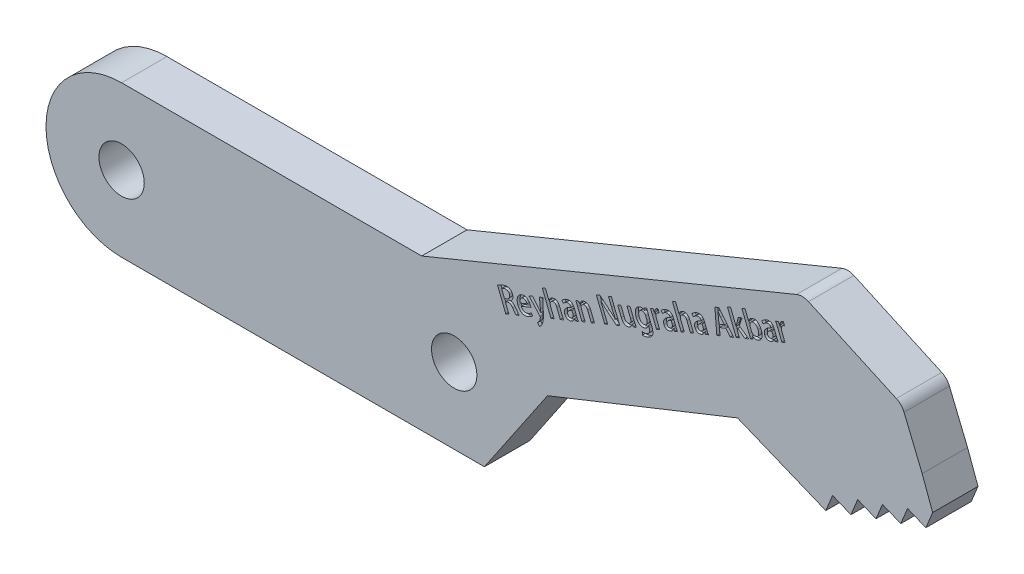
SolidWorks part; units mm, degrees
ref_plane "Front Plane" through (0, 0, 0) normal (0, 0, 1) x (1, 0, 0)
ref_plane "Top Plane" through (0, 0, 0) normal (0, 1, 0) x (1, 0, 0)
ref_plane "Right Plane" through (0, 0, 0) normal (1, 0, 0) x (0, 0, -1)
sketch "Sketch1" plane through (0, 0, 0) normal (0, 0, 1) x (1, 0, 0)
  line L0 (0, 0) -> (22, 0) construction
  line L1 (0, 5) -> (19.85, 5)
  line L2 (0, -5) -> (22, -5)
  line L3 (19.85, 5) -> (44.6431, 15.1937)
  line L4 (45.4379, 15.1788) -> (51.2451, 12.5335)
  line L5 (51.7554, 12.0038) -> (52.955, 9.0863)
  line L6 (24, -5) -> (22, -5)
  line L7 (24, -5) -> (28.1744, 1.1586)
  line L8 (28.1744, 1.1586) -> (40.742, 6.17)
  line L9 (40.742, 6.17) -> (46.5818, 3.7797)
  line L10 (46.5818, 3.7797) -> (47.0288, 4.8718)
  line L11 (47.0288, 4.8718) -> (48.2418, 4.3753)
  line L12 (48.2418, 4.3753) -> (48.6888, 5.4674)
  line L13 (48.6888, 5.4674) -> (49.9018, 4.9709)
  line L14 (49.9018, 4.9709) -> (50.3274, 6.0107)
  line L15 (50.3274, 6.0107) -> (51.5404, 5.5142)
  line L16 (51.5404, 5.5142) -> (51.9874, 6.6063)
  line L17 (51.9874, 6.6063) -> (53.2004, 6.1098)
  line L18 (53.2004, 6.1098) -> (53.6474, 7.2018)
  line L19 (53.6474, 7.2018) -> (52.955, 9.0863)
  arc A0 (0, 5) -> (0, -5) centre (0, 0) ccw
  circle A2 centre (0, 0) radius 1.5
  circle A3 centre (22, 0) radius 1.5
  arc A4 (51.2451, 12.5335) -> (51.7554, 12.0038) centre (50.8306, 11.6235) cw
  arc A5 (44.6431, 15.1937) -> (45.4379, 15.1788) centre (45.0233, 14.2688) cw
  point P3 (11, 0)
  point P18 (51.605, 12.3696)
  point P21 (45.0437, 15.3584)
  point P22 (24, -5)
  dimension "D3" = 3
  dimension "D4" = 3
  dimension "D12" = 1
  dimension "D2" = 5
  dimension "D5" = 19.85
  dimension "D6" = 157.65
  dimension "D7" = 27.24
  dimension "D8" = 133.16
  dimension "D9" = 7.21
  dimension "D10" = 136.84
  dimension "D11" = 3.55
  dimension "D13" = 24
  dimension "D14" = 55.87
  dimension "D15" = 7.44
  dimension "D16" = 214.13
  dimension "D17" = 13.53
  dimension "D18" = 224
  dimension "D19" = 6.31
  dimension "D20" = 1.18
  dimension "D21" = 1.66
  dimension "D22" = 2.0076
  dimension "D23" = 10
  dimension "D24" = 22
  dimension "D25" = 5
  dimension "D26" = 5
  dimension "D27" = 137.564
extrude "Boss-Extrude1" add sketch "Sketch1" along normal blind 3
sketch "Sketch2" plane through (0, 0, 3) normal (0, 0, 1) x (1, 0, 0)
  line L0 (25.266, 4.4107) -> (44.448, 12.2974) construction
  line L1 (44.6431, 15.1937) -> (19.85, 5) construction
  text T1 "Reyhan Nugraha Akbar" font "@Adobe Fan Heiti Std B" height 1.5
  point P0 (0, 0)
  point P5 (24.0477, 2.903)
  point P8 (22.7227, 3.3294)
  point P9 (23.3167, 4.1975)
  point P10 (44.8666, 11.2793)
  point P11 (29.8197, 4.2279)
  point P12 (27.7789, 4.8219)
  point P13 (26.1189, 4.3193)
  point P14 (25.7382, 4.1213)
  point P15 (25.266, 4.4107)
extrude "Cut-Extrude1" cut sketch "Sketch2" against normal blind 0.2
